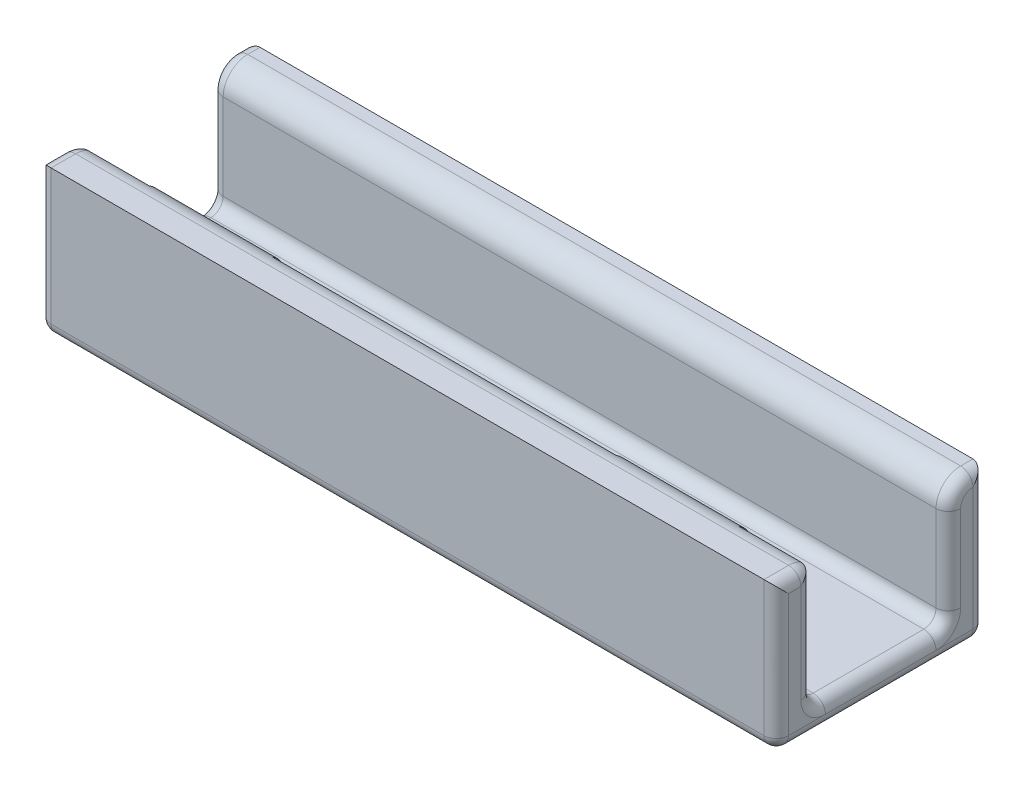
SolidWorks part; units mm, degrees
ref_plane "Front Plane" through (0, 0, 0) normal (0, 0, 1) x (1, 0, 0)
ref_plane "Top Plane" through (0, 0, 0) normal (0, 1, 0) x (1, 0, 0)
ref_plane "Right Plane" through (0, 0, 0) normal (1, 0, 0) x (0, 0, -1)
sketch "Sketch2" plane through (0, 0, 0) normal (0, 1, 0) x (1, 0, 0)
  line L1 (0, 0) -> (-60, 0)
  line L2 (0, 0) -> (0, -11)
  line L3 (0, -11) -> (-60, -11)
  line L4 (-60, 0) -> (-60, -11)
  line L5 (-60, -11) -> (0, -11)
  line L6 (-60, -11) -> (-60, -14)
  line L7 (-60, -14) -> (0, -14)
  line L8 (0, -11) -> (0, -14)
  line L9 (-60, 0) -> (0, 0)
  line L10 (-60, 0) -> (-60, 3)
  line L11 (-60, 3) -> (0, 3)
  line L12 (0, 0) -> (0, 3)
  dimension "D1" = 11
  dimension "D2" = 60
  dimension "D3" = 3
  dimension "D4" = 3
extrude "Boss-Extrude2" add sketch "Sketch2" along normal blind 2 contours L1 L12 L11 L10 | L1 L4 L3 L2 | L8 L3 L6 L7 region at (-30, 0, 5.5) region at (-30, 0, -1.5) region at (-30, 0, 12.5)
sketch "Sketch3" plane through (0, 2, 0) normal (0, 1, 0) x (1, 0, 0)
  line L1 (-60, 3) -> (0, 3)
  line L2 (-60, 3) -> (-60, -14)
  line L3 (-60, -14) -> (0, -14)
  line L4 (0, 3) -> (0, -14)
  line L5 (-60, 0) -> (0, 0)
  line L6 (-60, 0) -> (-60, -11)
  line L7 (-60, -11) -> (0, -11)
  line L8 (0, 0) -> (0, -11)
  line M5 (-60, 3) -> (-60, -14)
  line M6 (-60, -14) -> (0, -14)
  line M7 (0, -14) -> (0, 3)
  line M8 (0, 3) -> (-60, 3)
  dimension "D1" = 3
  dimension "D2" = 3
extrude "Boss-Extrude3" add sketch "Sketch3" along normal blind 10 contours L7 M5 M6 M7 | L5 L4 M5 M8 region at (-30, 2, -1.5) region at (-30, 2, 12.5)
ref_plane "Plane1" through (-30, 0, 0) normal (1, 0, 0) x (0, 0, -1)
sketch "Sketch4" plane through (0, 0, 11) normal (0, 0, -1) x (-1, 0, 0)
  line L0 (0, 12) -> (60, 12) construction
  line L5 (60, 12) -> (60, 0) construction
  line L6 (44, 12) -> (54, 12)
  line L7 (44, 12) -> (44, 10)
  line L8 (44, 10) -> (54, 10)
  line L9 (54, 12) -> (54, 10)
  line L10 (60, 2) -> (0, 2) construction
  line L11 (30, 6.6) -> (30, -6.6) construction
  line L12 (6, 12) -> (6, 10)
  line L13 (16, 10) -> (6, 10)
  line L14 (16, 12) -> (16, 10)
  line L15 (16, 12) -> (6, 12)
  dimension "D1" = 10
  dimension "D2" = 6
  dimension "D3" = 8
extrude "Boss-Extrude4" add sketch "Sketch4" along normal blind 1
fillet "Fillet1" radius 2 2 edges at (-30, 12, 0) (-11, 12, 10)
fillet "Fillet2" radius 1 24 edges at (-60, 2, 5.5) (-60, 6.866, 11) (-60, 11.9319, 11.4824) (-60, 12, 13) (-60, 6, 14) (-60, 0, 5.5) (-60, 6, -3) (-60, 12, -2.5) (-60, 11.4142, -0.5858) (-60, 6, 0) (0, 6, -3) (0, 0, 5.5) (0, 6, 14) (0, 12, 13) (0, 11.9319, 11.4824) (0, 6.866, 11) (0, 2, 5.5) (0, 6, 0) (0, 11.4142, -0.5858) (0, 12, -2.5) (-30, 0, 14) (-30, 0, -3) (-30, 2, 0) (-30, 2, 11)
